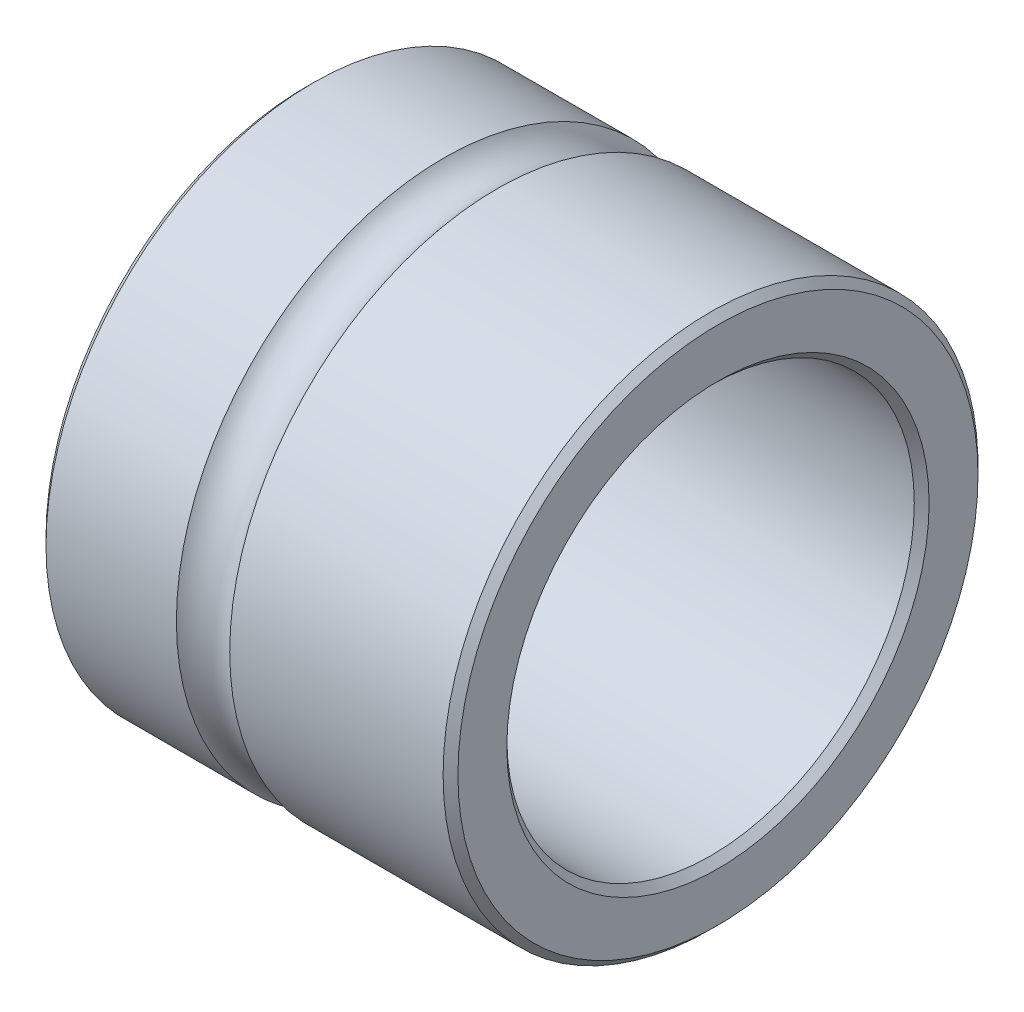
SolidWorks part; units mm, degrees
material "AISI 4130 钢，正火温度为 870C"
ref_plane "前视基准面" through (0, 0, 0) normal (0, 0, 1) x (1, 0, 0)
ref_plane "上视基准面" through (0, 0, 0) normal (0, 1, 0) x (1, 0, 0)
ref_plane "右视基准面" through (0, 0, 0) normal (1, 0, 0) x (0, 0, -1)
sketch "草图1" plane through (0, 0, 0) normal (0, 0, 1) x (1, 0, 0)
  line L0 (-55.0166, 0) -> (55.2805, 0) construction
  line L1 (0, 38.8) -> (0, 0) construction
  line L21 (-22.2, 27.5) -> (33.4, 27.5)
  line L22 (-22.2, 36.1) -> (-3.6, 36.1)
  line L23 (3.6, 36.1) -> (33.4, 36.1)
  line L25 (33.4, 36.1) -> (33.4, 27.5)
  line L26 (-22.2, 36.1) -> (-22.2, 27.5)
  arc A4 (-3.6, 36.1) -> (3.6, 36.1) centre (0, 38.8) ccw
  dimension "D5" = 4.5
  dimension "D1" = 27.5
  dimension "D2" = 22.2
  dimension "D3" = 55.6
  dimension "D4" = 36.1
  dimension "D6" = 38.8
revolve "旋转1" add sketch "草图1" angle 360 about L0
chamfer "倒角1" distance 1 angle 45 4 edges at (-22.2, 0, 36.1) (-22.2, 0, 27.5) (33.4, 0, 27.5) (33.4, 0, 36.1)
ref_axis "基准轴1" through (32.66, 0, 0) along (-1, 0, 0)
